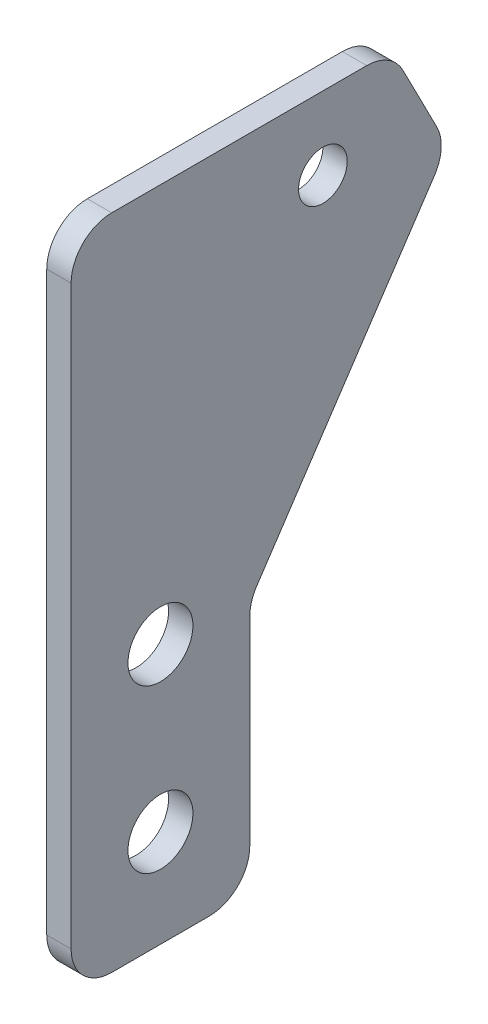
SolidWorks part; units mm, degrees
material "1023 Arkusz stali węglowej (SS)"
ref_plane "Płaszczyzna przednia" through (0, 0, 0) normal (0, 0, 1) x (1, 0, 0)
ref_plane "Płaszczyzna górna" through (0, 0, 0) normal (0, 1, 0) x (1, 0, 0)
ref_plane "Płaszczyzna prawa" through (0, 0, 0) normal (1, 0, 0) x (0, 0, -1)
sketch "Szkic1" plane through (0, 0, 0) normal (1, 0, 0) x (0, 0, -1)
  line L116 (316.4709, -192.7172) -> (347.8693, -192.7172)
  line L117 (316.4709, -273.7172) -> (328.4709, -273.7172)
  line L118 (356.4921, -203.5564) -> (352.3163, -195.4317)
  line L119 (311.4709, -197.7172) -> (311.4709, -268.7172)
  line L120 (334.3106, -241.4576) -> (356.2054, -208.6155)
  line L121 (333.4709, -244.2311) -> (333.4709, -268.7172)
  circle A57 centre (322.4709, -241.7172) radius 4
  circle A58 centre (322.4709, -261.7172) radius 4
  arc A59 (311.4709, -268.7172) -> (316.4709, -273.7172) centre (316.4709, -268.7172) ccw
  circle A60 centre (342.4709, -201.7172) radius 3
  arc A61 (316.4709, -192.7172) -> (311.4709, -197.7172) centre (316.4709, -197.7172) ccw
  arc A62 (352.3163, -195.4317) -> (347.8693, -192.7172) centre (347.8693, -197.7172) ccw
  arc A63 (328.4709, -273.7172) -> (333.4709, -268.7172) centre (328.4709, -268.7172) ccw
  arc A64 (356.2054, -208.6155) -> (356.4921, -203.5564) centre (352.0451, -205.842) ccw
  arc A65 (334.3106, -241.4576) -> (333.4709, -244.2311) centre (338.4709, -244.2311) ccw
extrude "Dodanie-wyciągnięcie1" add sketch "Szkic1" along normal blind 3
